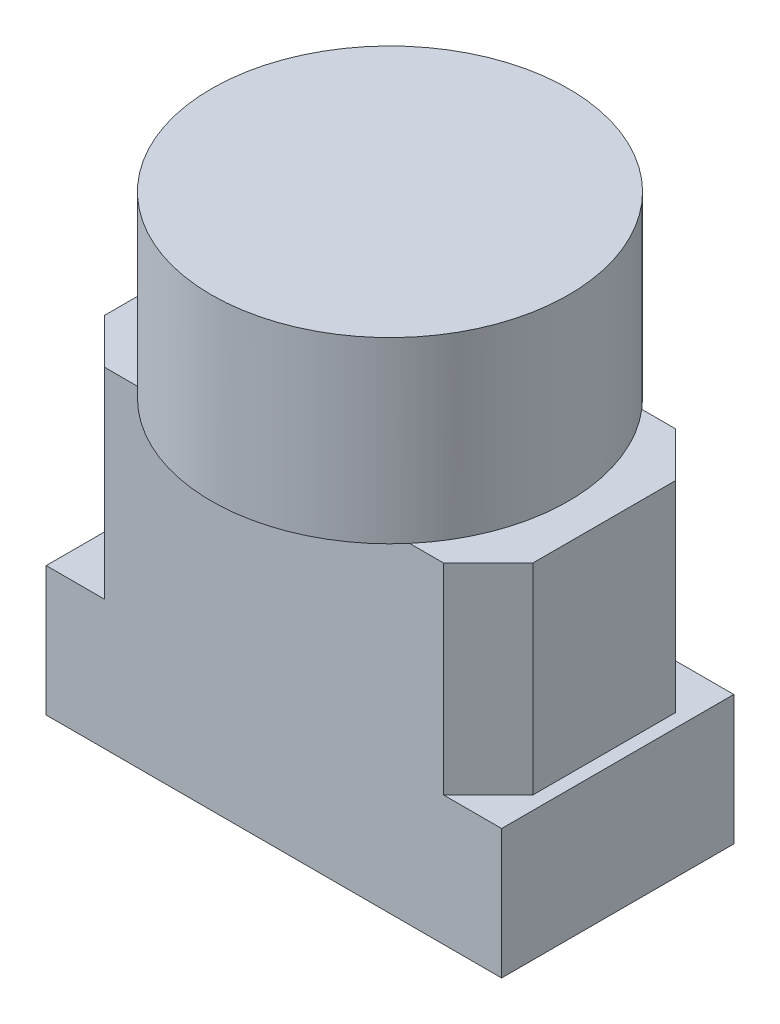
SolidWorks part; units mm, degrees
material "1060 Alloy"
ref_plane "Front Plane" through (0, 0, 0) normal (0, 0, 1) x (1, 0, 0)
ref_plane "Top Plane" through (0, 0, 0) normal (0, 1, 0) x (1, 0, 0)
ref_plane "Right Plane" through (0, 0, 0) normal (1, 0, 0) x (0, 0, -1)
sketch "Sketch1" plane through (0, 0, 0) normal (0, 1, 0) x (1, 0, 0)
  circle A0 centre (0, 0) radius 40
  dimension "D1" = 80
extrude "Boss-Extrude1" add sketch "Sketch1" along normal blind 40
sketch "Sketch2" plane through (0, 0, 0) normal (0, -1, 0) x (1, 0, 0)
  line L1 (48, 26) -> (-48, 26)
  line L2 (48, 26) -> (48, -26)
  line L3 (48, -26) -> (-48, -26)
  line L4 (-48, 26) -> (-48, -26)
  line L5 (48, 26) -> (-48, -26) construction
  line L6 (48, -26) -> (-48, 26) construction
  point P0 (0, 0)
  dimension "D1" = 96
  dimension "D2" = 52
extrude "Boss-Extrude2" add sketch "Sketch2" along normal blind 45
chamfer "Chamfer1" distance 10 angle 45 4 edges at (-48, -22.5, 26) (48, -22.5, 26) (-48, -22.5, -26) (48, -22.5, -26)
ref_point "Point1"
sketch "Sketch4" plane through (0, -45, 0) normal (0, -1, 0) x (-1, 0, 0)
  line L0 (38, 26) -> (-38, 26) construction
  line L1 (-51, -26) -> (51, -26)
  line L2 (-51, -26) -> (-51, 26)
  line L3 (-51, 26) -> (51, 26)
  line L4 (51, -26) -> (51, 26)
  line L5 (-51, -26) -> (51, 26) construction
  line L6 (-51, 26) -> (51, -26) construction
  point P0 (0, 0)
  dimension "D1" = 102
extrude "Boss-Extrude3" add sketch "Sketch4" along normal blind 33
chamfer "Chamfer2" distance 4 angle 45 4 edges at (51, -78, 0) (0, -78, 26) (-51, -78, 0) (0, -78, -26)
